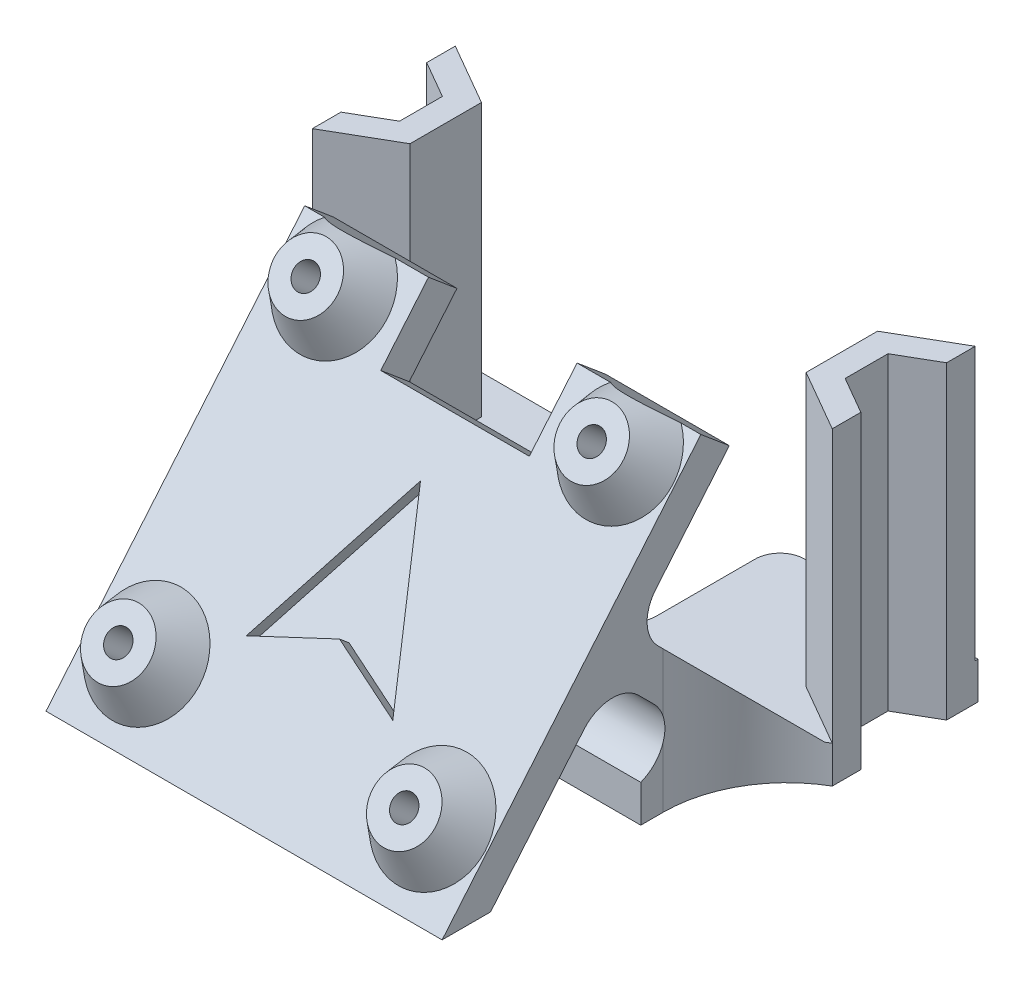
SolidWorks part; units mm, degrees
ref_plane "Спереди" through (0, 0, 0) normal (0, 0, 1) x (1, 0, 0)
ref_plane "Сверху" through (0, 0, 0) normal (0, 1, 0) x (1, 0, 0)
ref_plane "Справа" through (0, 0, 0) normal (1, 0, 0) x (0, 0, -1)
sketch "Эскиз2" plane through (0, 0, 0) normal (1, 0, 0) x (0, 0, -1)
  line L0 (0, 0) -> (-22.2426, 0)
  line L1 (-22.2426, 0) -> (-22.2426, 3)
  line L2 (-22.2426, 3) -> (-16.2426, 3)
  line L3 (-16.2426, 3) -> (-24.7333, 11.4907)
  line L4 (-24.7333, 11.4907) -> (-34.3751, 0)
  line L6 (-38.2913, 0) -> (-17.3896, 24.9097)
  line L7 (-17.3896, 24.9097) -> (-15.0915, 22.9813)
  line L8 (-15.0915, 22.9813) -> (-22.7976, 13.7976)
  line L9 (-22.7976, 13.7976) -> (-12, 3)
  line L10 (-12, 3) -> (0, 3)
  line L11 (0, 3) -> (0, 0)
  line L12 (-34.3751, 0) -> (-38.2913, 0)
  dimension "D1" = 3
  dimension "D2" = 3
  dimension "D3" = 30
  dimension "D4" = 3
  dimension "D5" = 3
  dimension "D6" = 45
  dimension "D7" = 85
  dimension "D8" = 15
  dimension "D9" = 3
  dimension "D10" = 12
  dimension "D11" = 6
extrude "Бобышка-Вытянуть1" add sketch "Эскиз2" along normal blind 50
sketch "Эскиз3" plane through (0, 3, 0) normal (0, 1, 0) x (1, 0, 0)
  line L0 (25, 0) -> (25, -38.2913) construction
  line L1 (4, -2.5359) -> (1, -4.2679)
  line L2 (1, -4.2679) -> (1, -7.7321)
  line L3 (1, -7.7321) -> (4, -9.4641)
  line L4 (4, -9.4641) -> (7, -7.7321)
  line L5 (7, -7.7321) -> (7, -4.2679)
  line L6 (7, -4.2679) -> (4, -2.5359)
  line L7 (46, -2.5359) -> (43, -4.2679)
  line L8 (43, -4.2679) -> (43, -7.7321)
  line L9 (43, -7.7321) -> (46, -9.4641)
  line L10 (46, -9.4641) -> (49, -7.7321)
  line L11 (49, -7.7321) -> (49, -4.2679)
  line L12 (49, -4.2679) -> (46, -2.5359)
  line L13 (50, 0) -> (0, 0) construction
  line L15 (4, -2.5359) -> (4, -6) construction
  line L16 (46, -2.5359) -> (46, -6) construction
  line L18 (50, -38.2913) -> (0, -38.2913) construction
  circle A0 centre (4, -6) radius 3 construction
  circle A1 centre (46, -6) radius 3 construction
  dimension "D1" = 6
  dimension "D2" = 6
  dimension "D3" = 42
  dimension "D4" = 21
  dimension "D5" = 6
extrude "Вырез-Вытянуть1" cut sketch "Эскиз3" against normal through all
sketch "Эскиз5" plane through (0, 3, 0) normal (0, 1, 0) x (1, 0, 0)
  line L0 (25, 0) -> (25, -38.2913) construction
  line L1 (50, 0) -> (0, 0) construction
  line L3 (4, -2.5359) -> (4, -9.4641) construction
  line L4 (46, -2.5359) -> (46, -9.4641) construction
  line L5 (4, -6) -> (46, -6) construction
  line L6 (4, -6) -> (4, -0.2265) construction
  line L7 (4, -2.5359) -> (1, -4.2679)
  line L8 (1, -4.2679) -> (1, -7.7321)
  line L9 (1, -7.7321) -> (4, -9.4641)
  line L10 (4, -9.4641) -> (7, -7.7321)
  line L11 (7, -7.7321) -> (7, -4.2679)
  line L12 (7, -4.2679) -> (4, -2.5359)
  line L13 (46, -2.5359) -> (43, -4.2679)
  line L14 (43, -4.2679) -> (43, -7.7321)
  line L15 (43, -7.7321) -> (46, -9.4641)
  line L16 (46, -9.4641) -> (49, -7.7321)
  line L17 (49, -7.7321) -> (49, -4.2679)
  line L18 (49, -4.2679) -> (46, -2.5359)
  line L19 (4, -0.2265) -> (-1, -3.1132)
  line L20 (-1, -3.1132) -> (-1, -8.8868)
  line L21 (-1, -8.8868) -> (4, -11.7735)
  line L22 (4, -11.7735) -> (9, -8.8868)
  line L23 (9, -8.8868) -> (9, -3.1132)
  line L24 (9, -3.1132) -> (4, -0.2265)
  line L25 (46, -0.2265) -> (41, -3.1132)
  line L26 (41, -3.1132) -> (41, -8.8868)
  line L27 (41, -8.8868) -> (46, -11.7735)
  line L28 (46, -11.7735) -> (51, -8.8868)
  line L29 (51, -8.8868) -> (51, -3.1132)
  line L30 (51, -3.1132) -> (46, -0.2265)
  line L31 (46, -6) -> (46, -0.2265) construction
  line L32 (50, -38.2913) -> (0, -38.2913) construction
  circle A0 centre (4, -6) radius 3 construction
  circle A1 centre (46, -6) radius 3 construction
  circle A2 centre (4, -6) radius 5 construction
  circle A3 centre (46, -6) radius 5 construction
  dimension "D1" = 10
  dimension "D2" = 10
extrude "Бобышка-Вытянуть2" add sketch "Эскиз5" along normal blind 22
sketch "Эскиз6" plane through (0, 0, 0) normal (0, -1, 0) x (1, 0, 0)
  line L0 (46, 0) -> (46, 38.2913)
  line L2 (50, 0) -> (0, 0) construction
  line L8 (50, 38.2913) -> (0, 38.2913) construction
  line L9 (46, 38.2913) -> (51, 38.2913)
  line L14 (51, 38.2913) -> (51, 0)
  line L15 (51, 0) -> (46, 0)
  line L16 (51, 8.8868) -> (51, 3.1132) construction
  line L17 (4, 0) -> (4, 38.2913)
  line L18 (4, 38.2913) -> (-1, 38.2913)
  line L19 (-1, 38.2913) -> (-1, 0)
  line L20 (-1, 0) -> (4, 0)
  line L21 (-1, 3.1132) -> (-1, 8.8868) construction
extrude "Вырез-Вытянуть5" cut sketch "Эскиз6" against normal blind 50
sketch "Эскиз8" plane through (0, 18.8548, 22.4703) normal (0, 0.6428, 0.766) x (1, 0, 0)
  line L0 (4, -7.0959) -> (46, -7.0959) construction
  line L2 (25, 7.9041) -> (25, -24.6132) construction
  line L3 (46, 7.9041) -> (4, 7.9041) construction
  line L5 (46, -24.6132) -> (4, -24.6132) construction
  circle A0 centre (36.55, 4.6841) radius 2.5
  circle A1 centre (36.55, 4.6841) radius 1
  circle A2 centre (13.45, 4.6841) radius 2.5
  circle A3 centre (13.45, 4.6841) radius 1
  circle A4 centre (13.45, -18.8759) radius 2.5
  circle A5 centre (13.45, -18.8759) radius 1
  circle A6 centre (36.55, -18.8759) radius 2.5
  circle A7 centre (36.55, -18.8759) radius 1
  dimension "D1" = 2
  dimension "D2" = 5
  dimension "D3" = 2
  dimension "D4" = 5
  dimension "D5" = 2
  dimension "D6" = 5
  dimension "D7" = 2
  dimension "D8" = 5
  dimension "D9" = 23.1
  dimension "D10" = 15
  dimension "D11" = 23.56
  dimension "D12" = 11.78
  dimension "D13" = 11.55
extrude "Бобышка-Вытянуть4" add sketch "Эскиз8" along normal blind 3
chamfer "Фаска1" distance 1.8 angle 60 4 edges at (36.55, 6.3101, 32.9965) (13.45, 6.3101, 32.9965) (36.55, 24.3581, 17.8524) (13.45, 24.3581, 17.8524) first distance on face at (36.55, 6.3101, 32.9965)
sketch "Эскиз9" plane through (0, 3, 0) normal (0, 1, 0) x (1, 0, 0)
  line L0 (25, 0) -> (25, -38.2913) construction
  line L1 (46, 0) -> (4, 0) construction
  line L3 (46, -38.2913) -> (4, -38.2913) construction
  line L4 (20, -12) -> (30, -12)
  line L5 (20, -12) -> (20, 0)
  line L6 (20, 0) -> (30, 0)
  line L7 (30, -12) -> (30, 0)
  line L8 (20, -12) -> (30, 0) construction
  line L9 (20, 0) -> (30, -12) construction
  point P6 (25, -6)
  dimension "D1" = 10
  dimension "D2" = 12
  dimension "D3" = 6
extrude "Вырез-Вытянуть6" cut sketch "Эскиз9" against normal blind 3
sketch "Эскиз10" plane through (0, 18.8548, 22.4703) normal (0, 0.6428, 0.766) x (1, 0, 0)
  line L0 (25, 7.9041) -> (25, -24.6132) construction
  line L1 (33.7002, 7.9041) -> (16.2998, 7.9041) construction
  line L3 (19, 7.9041) -> (19, 1.9041)
  line L4 (19, 1.9041) -> (31, 1.9041)
  line L5 (31, 1.9041) -> (31, 7.9041)
  line L6 (19, 7.9041) -> (31, 7.9041)
  line L7 (46, -24.6132) -> (4, -24.6132) construction
  dimension "D1" = 6
  dimension "D2" = 12
  dimension "D3" = 6
extrude "Вырез-Вытянуть7" cut sketch "Эскиз10" against normal blind 3
fillet "Скругление2" radius 3 1 edges at (25, 11.4907, 24.7333)
fillet "Скругление3" radius 3 1 edges at (25, 3, 16.2426)
fillet "Скругление4" radius 3 1 edges at (25, 13.7976, 22.7976)
sketch "Эскиз11" plane through (0, 18.8548, 22.4703) normal (0, 0.6428, 0.766) x (1, 0, 0)
  line L0 (25, 1.9041) -> (25, -24.6132) construction
  line L1 (19, 1.9041) -> (31, 1.9041) construction
  line L3 (25, -2.4364) -> (19.0833, -15.1247)
  line L4 (19.0833, -15.1247) -> (25, -12.6132)
  line L5 (25, -2.4364) -> (30.9167, -15.1247)
  line L6 (30.9167, -15.1247) -> (25, -12.6132)
  line L7 (46, -24.6132) -> (4, -24.6132) construction
  dimension "D1" = 25
  dimension "D2" = 42
  dimension "D3" = 14
  dimension "D4" = 12
  dimension "D5" = 6.4276
  dimension "D6" = 14
  dimension "D7" = 50
extrude "Вырез-Вытянуть8" cut sketch "Эскиз11" against normal blind 1
fillet "Скругление7" radius 2 4 edges at (20, 1.5, 12) (30, 1.5, 12) (30, 1.5, 0) (20, 1.5, 0)
sketch "Эскиз12" plane through (0, 0, 0) normal (0, -1, 0) x (1, 0, 0)
  line L0 (4, 11.7735) -> (9, 11.7735)
  line L1 (9, 11.7735) -> (9, 38.2913)
  line L2 (46, 38.2913) -> (4, 38.2913) construction
  line L3 (9, 38.2913) -> (4, 38.2913)
  line L4 (4, 38.2913) -> (4, 11.7735)
  line L5 (46, 11.7735) -> (41, 11.7735)
  line L6 (41, 11.7735) -> (41, 38.2913)
  line L7 (41, 38.2913) -> (46, 38.2913)
  line L8 (46, 38.2913) -> (46, 11.7735)
  line L9 (46, 9.4641) -> (46, 11.7735) construction
  dimension "D1" = 5
  dimension "D2" = 5
extrude "Вырез-Вытянуть9" cut sketch "Эскиз12" against normal through all
fillet "Скругление8" radius 10 2 edges at (41, 1.5, 11.7735) (9, 1.5, 11.7735)
